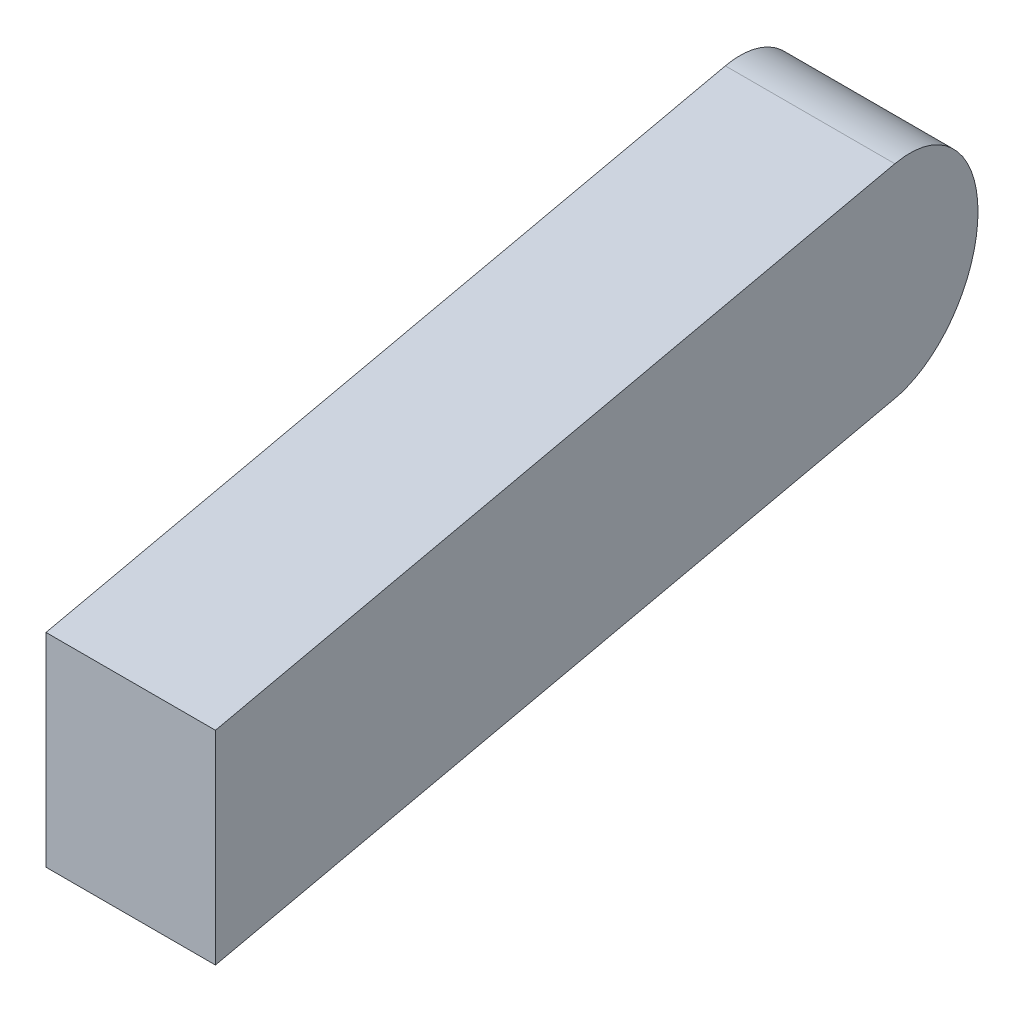
SolidWorks part; units mm, degrees
ref_plane "Front Plane" through (0, 0, 0) normal (0, 0, 1) x (1, 0, 0)
ref_plane "Top Plane" through (0, 0, 0) normal (0, 1, 0) x (1, 0, 0)
ref_plane "Right Plane" through (0, 0, 0) normal (1, 0, 0) x (0, 0, -1)
sketch "Sketch1" plane through (0, 0, 0) normal (0, 1, 0) x (1, 0, 0)
  line L0 (0, 0) -> (1, 0)
  line L1 (1, 0) -> (0, 5.5)
  line L2 (0, 5.5) -> (-1, 5.5)
  line L3 (-1, 5.5) -> (0, 0)
  dimension "D1" = 1
  dimension "D2" = 5.5
extrude "Boss-Extrude1" add sketch "Sketch1" along normal mid plane 1.2
ref_axis "Axis2" through (0, 0, -5.5) along (0, 0, 1)
sketch "Sketch4" plane through (0, 0, 0) normal (1, 0, 0) x (0, 0, -1)
  line L0 (5.5, 0) -> (0, 0) construction
  line L1 (5.5, 0.6) -> (5.5, -0.6) construction
  line L3 (0, 0.6) -> (5.5, 0.6) construction
  line L4 (0, -0.6) -> (5.5, -0.6) construction
  line L5 (4.9, -0.6) -> (5.5, -0.6)
  line L7 (5.5, 0) -> (5.5, -0.6)
  arc A0 (4.9, -0.6) -> (5.5, 0) centre (4.9, 0) ccw
extrude "Cut-Extrude1" cut sketch "Sketch4" against normal through all both and the other way through all
mirror "Mirror1" about plane through (0, 0, 0) normal (0, 1, 0) of "Cut-Extrude1"
